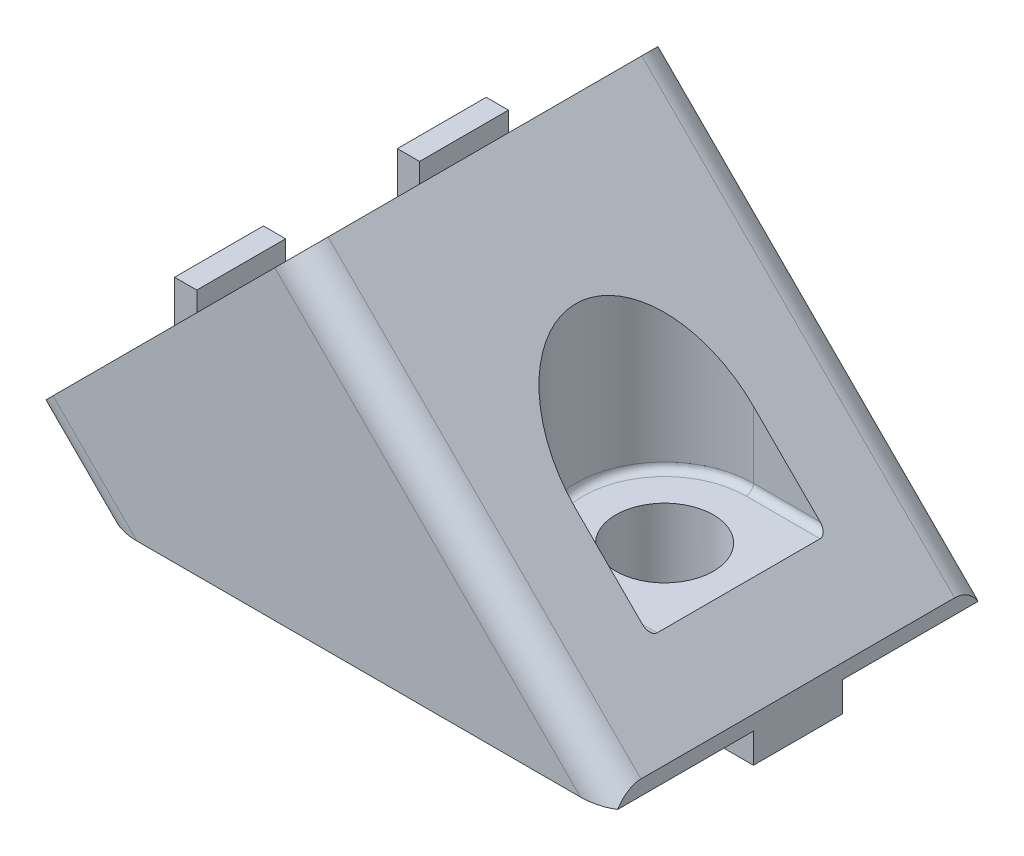
SolidWorks part; units mm, degrees
ref_plane "Front Plane" through (0, 0, 0) normal (0, 0, 1) x (1, 0, 0)
ref_plane "Top Plane" through (0, 0, 0) normal (0, 1, 0) x (1, 0, 0)
ref_plane "Right Plane" through (0, 0, 0) normal (1, 0, 0) x (0, 0, -1)
sketch "Sketch1" plane through (0, 0, 0) normal (0, 0, 1) x (1, 0, 0)
  line L0 (0, 0) -> (-4.1719, 4.1719)
  line L1 (34.921, 1) -> (13.7886, 22.1324)
  line L2 (34.921, 0) -> (34.921, 1)
  line L3 (34.921, 1) -> (35.921, 0) construction
  line L4 (13.7886, 22.1324) -> (-4.1719, 4.1719)
  line L5 (34.921, 0) -> (0, 0)
  line L6 (34.921, 0) -> (35.921, 0) construction
  dimension "D2" = 25.4
  dimension "D3" = 31.3
  dimension "D1" = 45
  dimension "D4" = 1
extrude "Boss-Extrude1" add sketch "Sketch1" along normal mid plane 25.4
sketch "Sketch2" plane through (0, 0, 0) normal (0, 1, 0) x (1, 0, 0)
  line L0 (35.921, 0) -> (25.921, 0) construction
  line L2 (35.921, -12.7) -> (35.921, 12.7) construction
  circle A0 centre (25.921, 0) radius 3.3
  circle A1 centre (25.921, 0) radius 6 construction
  dimension "D2" = 6.6
  dimension "D3" = 12
  dimension "D1" = 10
extrude "Cut-Extrude1" cut sketch "Sketch2" against normal through all from offset 5
sketch "Sketch3" plane through (0, 5, 0) normal (0, -1, 0) x (1, 0, 0)
  line L0 (25.921, -6) -> (35.921, -6)
  line L2 (25.921, 6) -> (35.921, 6)
  line L3 (35.921, 6) -> (35.921, -6)
  arc A0 (25.921, 6) -> (25.921, -6) centre (25.921, 0) ccw
  circle A1 centre (25.921, 0) radius 6 construction
extrude "Cut-Extrude2" cut sketch "Sketch3" against normal through all
fillet "Fillet1" radius 2.1082 4 edges at (-2.086, 2.086, -12.7) (-2.086, 2.086, 12.7) (24.3548, 11.5662, -12.7) (24.3548, 11.5662, 12.7)
fillet "Fillet2" radius 0.5 3 edges at (28.421, 5, 6) (28.421, 5, -6) (19.921, 5, 0)
sketch "Sketch4" plane through (0, 0, 0) normal (0, 0, 1) x (1, 0, 0)
  line L0 (34.921, 0) -> (0, 0) construction
  line L1 (7.5, 0) -> (0, 0)
  line L2 (7.5, 0) -> (7.5, -2)
  line L3 (7.5, -2) -> (0, -2)
  line L4 (0, 0) -> (0, -2)
  line L5 (13.7886, 22.1324) -> (-4.1719, 4.1719) construction
  line L6 (31.921, 0) -> (34.921, 0)
  line L7 (31.921, 0) -> (31.921, -2)
  line L8 (31.921, -2) -> (34.921, -2)
  line L9 (34.921, 0) -> (34.921, -2)
  line L10 (-4.1719, 7.0004) -> (-2.6719, 7.0004)
  line L11 (-4.1719, 7.0004) -> (-4.1719, 4.1719)
  line L12 (-4.1719, 4.1719) -> (-2.6719, 5.6719)
  line L13 (-2.6719, 7.0004) -> (-2.6719, 5.6719)
  line L14 (10.8744, 22.0467) -> (12.3744, 22.0467)
  line L15 (10.8744, 22.0467) -> (10.8744, 19.2182)
  line L16 (10.8744, 19.2182) -> (12.3744, 20.7182)
  line L17 (12.3744, 22.0467) -> (12.3744, 20.7182)
  line L18 (34.921, 1) -> (13.7886, 22.1324) construction
  dimension "D1" = 7.5
  dimension "D2" = 3
  dimension "D3" = 2
  dimension "D4" = 2
  dimension "D5" = 1.5
  dimension "D6" = 1.5
  dimension "D7" = 2
  dimension "D8" = 2
  dimension "D9" = 2
extrude "Boss-Extrude4" add sketch "Sketch4" along normal mid plane 6
sketch "Sketch5" plane through (-4.1719, 4.1719, 0) normal (-0.7071, 0.7071, 0) x (0, 0, 1)
  line L0 (0, 0) -> (0, 12.7) construction
  line L1 (3, 0) -> (-3, 0) construction
  circle A0 centre (0, 12.7) radius 3.3
  circle A1 centre (0, 12.7) radius 4.25 construction
  dimension "D2" = 6.6
  dimension "D3" = 8.5
  dimension "D1" = 12.7
extrude "Cut-Extrude3" cut sketch "Sketch5" along normal through all from offset 5 offset against normal yes
sketch "Sketch6" plane through (-0.6364, 0.6364, 0) normal (-0.7071, 0.7071, 0) x (0, 0, 1)
  line L0 (-4.25, 12.7) -> (-4.25, 8.45)
  line L1 (4.25, 12.7) -> (4.25, 8.45)
  line L2 (4.25, 8.45) -> (-4.25, 8.45)
  arc A0 (4.25, 12.7) -> (-4.25, 12.7) centre (0, 12.7) ccw
  circle A1 centre (0, 12.7) radius 4.25 construction
extrude "Cut-Extrude4" cut sketch "Sketch6" against normal through all draft 1
sketch "Sketch7" plane through (0, 0, 0) normal (0, 0, 1) x (1, 0, 0)
  line L0 (7.5, -2) -> (7.5, 0) construction
  line L1 (12.185, 0) -> (7.5, 0)
  line L3 (12.185, 0) -> (5.3387, 6.6114)
  line L4 (7.5, 0) -> (5.3387, 6.6114)
  line L5 (2.9814, 0) -> (32.9396, 0) construction
  line L6 (12.185, 0) -> (5.3387, 6.6114) construction
  line L7 (5.3387, 6.6114) -> (8.3439, 9.6167) construction
extrude "Cut-Extrude5" cut sketch "Sketch7" along normal up to surface and the other way up to surface up to face at (10.957, 4.057, 4.1491) other way up to face at (10.957, 4.057, -4.1491)
fillet "Fillet3" radius 0.5 3 edges at (6.8413, 8.1141, 4.25) (6.8413, 8.1141, -4.25) (11.3491, 12.6219, 0)
fillet "Fillet4" radius 0.5 3 edges at (6.508, 3.0346, 4.1914) (6.508, 3.0346, -4.1914) (5.3908, 6.4521, -4.0978)
equation "\"D1@Sketch5\" = \"D2@Sketch1\" / 2"
